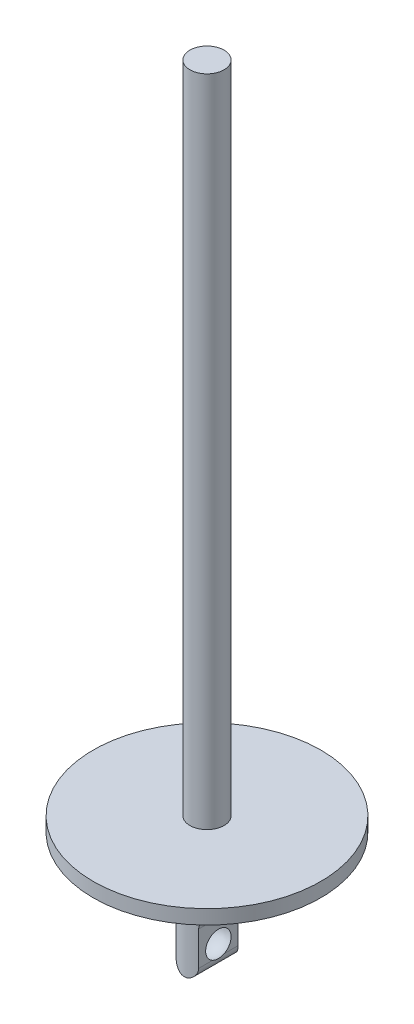
SolidWorks part; units mm, degrees
ref_plane "Piano frontale" through (0, 0, 0) normal (0, 0, 1) x (1, 0, 0)
ref_plane "Piano superiore" through (0, 0, 0) normal (0, 1, 0) x (1, 0, 0)
ref_plane "Piano destro" through (0, 0, 0) normal (1, 0, 0) x (0, 0, -1)
sketch "Schizzo1" plane through (0, 0, 0) normal (0, 1, 0) x (1, 0, 0)
  circle A0 centre (0, 0) radius 8
extrude "Estrusione-Estrusione1" add sketch "Schizzo1" along normal blind 40
sketch "Schizzo2" plane through (0, 40, 0) normal (0, 1, 0) x (1, 0, 0)
  circle A0 centre (0, 0) radius 40
extrude "Estrusione-Estrusione2" add sketch "Schizzo2" along normal blind 5
sketch "Schizzo3" plane through (0, 45, 0) normal (0, 1, 0) x (1, 0, 0)
  circle A0 centre (0, 0) radius 6
extrude "Estrusione-Estrusione3" add sketch "Schizzo3" along normal blind 230
sketch "Schizzo4" plane through (0, 0, 0) normal (0, 0, 1) x (1, 0, 0)
  line L1 (8, 0) -> (4, 0)
  line L2 (8, 0) -> (8, 20)
  line L3 (8, 20) -> (4, 20)
  line L4 (4, 0) -> (4, 20)
  dimension "D1" = 20
  dimension "D2" = 4
extrude "Taglio-Estrusione1" cut sketch "Schizzo4" against normal through all and the other way through all
mirror "Specchia1" about plane through (0, 0, 0) normal (1, 0, 0) of "Taglio-Estrusione1"
ref_plane "Piano1" through (0, 0, 0) normal (1, 0, 0) x (0, 0, -1)
sketch "Schizzo5" plane through (0, 0, 0) normal (1, 0, 0) x (0, 0, -1)
  line L0 (-6, 8) -> (6, 8)
  arc A0 (6, 8) -> (-6, 8) centre (0, 8) ccw
  dimension "D1" = 8
  dimension "D2" = 12
  dimension "D3" = 0
  dimension "D4" = 0
revolve "Rivoluzione1" add sketch "Schizzo5" angle 360 about L0
combine bodies "Abbina1" operation type subtract main body 106 bodies to subtract 107
fillet "Raccordo1" radius 4 4 edges at (-4, 0, 0) (4, 0, 0) (4, 20, 0) (-4, 20, 0)
